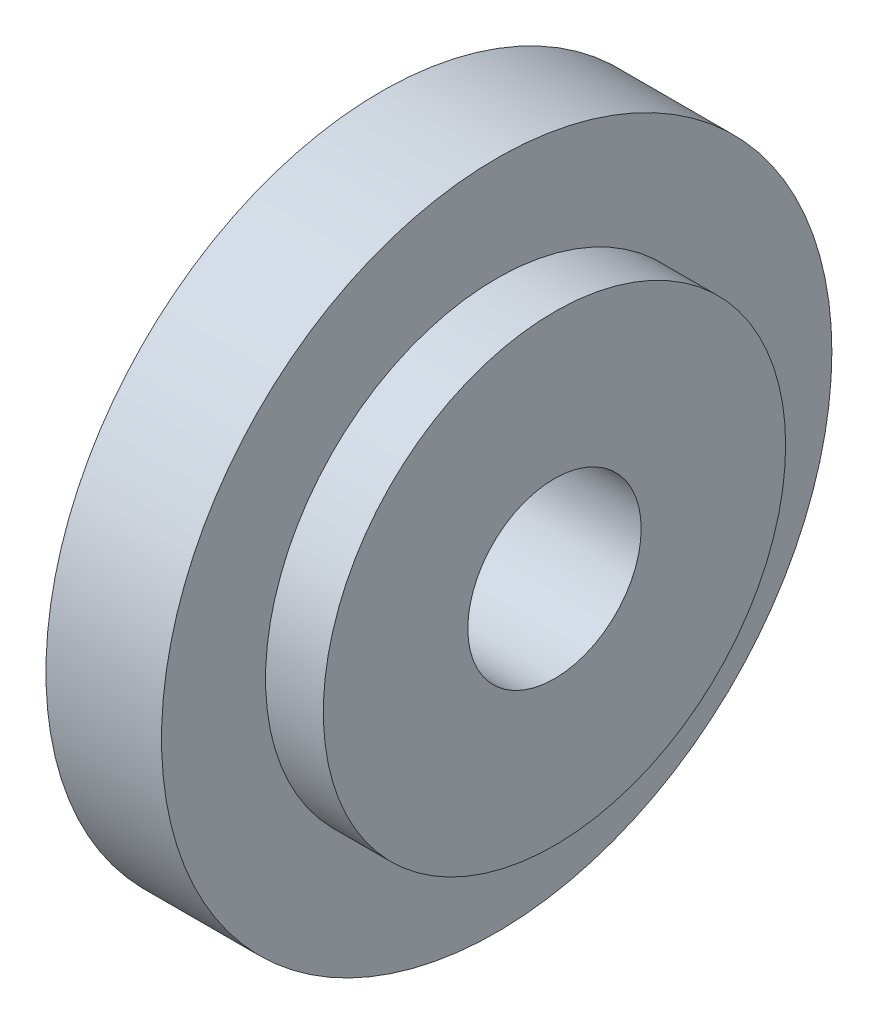
SolidWorks part; units mm, degrees
ref_plane "Front Plane" through (0, 0, 0) normal (0, 0, 1) x (1, 0, 0)
ref_plane "Top Plane" through (0, 0, 0) normal (0, 1, 0) x (1, 0, 0)
ref_plane "Right Plane" through (0, 0, 0) normal (1, 0, 0) x (0, 0, -1)
sketch "Sketch1" plane through (0, 0, 0) normal (1, 0, 0) x (0, 0, -1)
  circle A0 centre (0, 0) radius 5.8
extrude "Boss-Extrude1" add sketch "Sketch1" along normal blind 2
sketch "Sketch2" plane through (2, 0, 0) normal (1, 0, 0) x (0, 0, -1)
  circle A0 centre (0, 0) radius 4
extrude "Boss-Extrude2" add sketch "Sketch2" along normal blind 1
sketch "Sketch3" plane through (0, 0, 0) normal (-1, 0, 0) x (0, 0, 1)
  circle A0 centre (0, 0) radius 1.5
extrude "Cut-Extrude1" cut sketch "Sketch3" against normal blind 20
